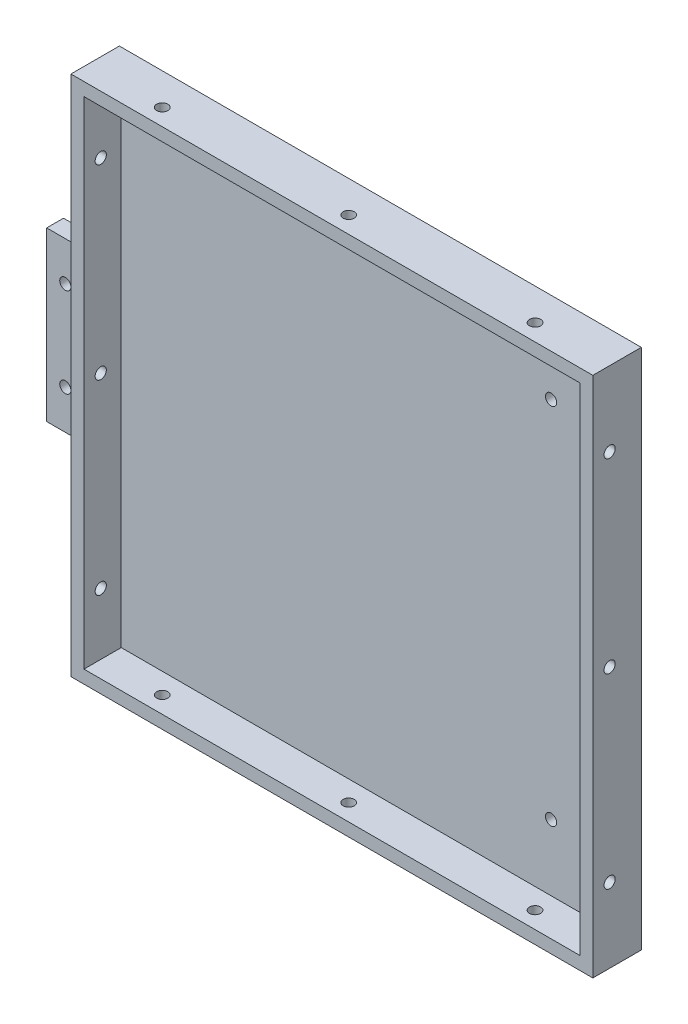
SolidWorks part; units mm, degrees
ref_plane "前视基准面" through (0, 0, 0) normal (0, 0, 1) x (1, 0, 0)
ref_plane "上视基准面" through (0, 0, 0) normal (0, 1, 0) x (1, 0, 0)
ref_plane "右视基准面" through (0, 0, 0) normal (1, 0, 0) x (0, 0, -1)
sketch "草图3" plane through (0, 0, 0) normal (0, 0, 1) x (1, 0, 0)
  line L1 (70, -70) -> (-70, -70)
  line L2 (70, -70) -> (70, 70)
  line L3 (70, 70) -> (-70, 70)
  line L4 (-70, -70) -> (-70, 70)
  line L5 (70, -70) -> (-70, 70) construction
  line L6 (70, 70) -> (-70, -70) construction
  point P0 (0, 0)
  dimension "D1" = 140
  dimension "D2" = 140
extrude "凸台-拉伸2" add sketch "草图3" along normal blind 3
sketch "草图4" plane through (0, 0, 3) normal (0, 0, 1) x (1, 0, 0)
  line L0 (70, -70) -> (70, 70) construction
  line L1 (66.5, -66.5) -> (-66.5, -66.5)
  line L2 (66.5, -66.5) -> (66.5, 66.5)
  line L3 (66.5, 66.5) -> (-66.5, 66.5)
  line L4 (-66.5, -66.5) -> (-66.5, 66.5)
  line L5 (66.5, -66.5) -> (-66.5, 66.5) construction
  line L6 (66.5, 66.5) -> (-66.5, -66.5) construction
  line L7 (-70, -70) -> (70, -70) construction
  line L12 (-70, 70) -> (-70, -70)
  line L13 (-70, -70) -> (70, -70)
  line L14 (70, -70) -> (70, 70)
  line L15 (70, 70) -> (-70, 70)
  line L16 (-70, 70) -> (-70, -70)
  line L17 (-70, -70) -> (70, -70)
  line L18 (70, -70) -> (70, 70)
  line L19 (70, 70) -> (-70, 70)
  point P0 (0, 0)
  point P6 (66.5, 0)
  dimension "D1" = 3.5
  dimension "D2" = 3.5
  dimension "D3" = 0
extrude "凸台-拉伸3" add sketch "草图4" along normal blind 10 contours L16 L17 L18 L19 | L2 L1 L4 L3
sketch "草图7" plane through (0, -70, 0) normal (0, -1, 0) x (1, 0, 0)
  line L0 (0, 13) -> (0, 8.5) construction
  line L1 (-70, 13) -> (70, 13) construction
  circle A0 centre (0, 8.5) radius 1.5
  circle A1 centre (50, 8.5) radius 1.5
  circle A2 centre (-50, 8.5) radius 1.5
  dimension "D2" = 3
  dimension "D1" = 4.5
  dimension "D3" = 2
  dimension "D4" = 2
extrude "切除-拉伸1" cut sketch "草图7" against normal through all
sketch "草图9" plane through (-70, 0, 0) normal (-1, 0, 0) x (0, 0, 1)
  line L0 (13, 0) -> (8.5, 0) construction
  line L1 (13, 70) -> (13, -70) construction
  circle A0 centre (8.5, 0) radius 1.5
  circle A1 centre (8.5, -50) radius 1.5
  circle A2 centre (8.5, 50) radius 1.5
  dimension "D2" = 3
  dimension "D1" = 4.5
  dimension "D3" = 2
  dimension "D4" = 2
extrude "切除-拉伸2" cut sketch "草图9" against normal through all
sketch "草图10" plane through (0, 0, 0) normal (0, 0, -1) x (-1, 0, 0)
  line L0 (70, -70) -> (-70, -70) construction
  line L1 (22.5, -85) -> (-22.5, -85)
  line L2 (22.5, -85) -> (22.5, -70)
  line L4 (-22.5, -85) -> (-22.5, -70)
  line L5 (22.5, -85) -> (-23.9974, -54.0017) construction
  line L6 (23.9974, -54.0017) -> (-22.5, -85) construction
  line L7 (-22.5, -70) -> (22.5, -70)
  point P0 (0, -70)
  dimension "D1" = 45
  dimension "D2" = 15
extrude "凸台-拉伸4" add sketch "草图10" against normal blind 4.5
sketch "草图11" plane through (0, 0, 4.5) normal (0, 0, 1) x (1, 0, 0)
  line L0 (0, -85) -> (0, -80)
  line L1 (22.5, -85) -> (-22.5, -85) construction
  line L2 (0, -80) -> (-12, -80) construction
  circle A0 centre (-12, -80) radius 1.5
  circle A1 centre (12, -80) radius 1.5
  dimension "D3" = 3
  dimension "D1" = 5
  dimension "D2" = 12
extrude "切除-拉伸3" cut sketch "草图11" against normal through all contours A0 | A1 region at (-12, -80, 4.5) region at (12, -80, 4.5)
sketch "草图12" plane through (0, 0, 13) normal (0, 0, 1) x (1, 0, 0)
  line L0 (-70, -70) -> (-66.5, -66.5) construction
ref_axis "基准轴1" through (0, 0, 13.65) along (0, 0, -1)
pattern_circular "阵列(圆周)1" count 2 every 90 about axis through (0, 0, 13.65) along (0, 0, -1) of "凸台-拉伸4", "切除-拉伸3"
fillet "圆角1" radius 8 6 edges at (22.5, -70, 2.25) (-22.5, -70, 2.25) (0, -70, 4.5) (-70, -22.5, 2.25) (-70, 22.5, 2.25) (-70, 0, 4.5)
sketch "草图13" plane through (-70, 0, 0) normal (-1, 0, 0) x (0, 0, 1)
  circle A0 centre (8.5, 0) radius 3
  dimension "D1" = 6
extrude "切除-拉伸4" cut sketch "草图13" along normal through all
sketch "草图14" plane through (0, -70, 0) normal (0, -1, 0) x (1, 0, 0)
  circle A0 centre (0, 8.5) radius 2.0492
extrude "切除-拉伸6" cut sketch "草图14" along normal through all contours A0
sketch "草图15" plane through (0, 0, 0) normal (0, 0, -1) x (-1, 0, 0)
  line L0 (-30.5, -70) -> (-70, -70) construction
  line L1 (-30.5, -70) -> (29.6234, -70)
  line L2 (-30.5, -70) -> (-30.5, -85.1765)
  line L3 (-30.5, -85.1765) -> (29.6234, -85.1765)
  line L4 (29.6234, -70) -> (29.6234, -85.1765)
extrude "切除-拉伸7" cut sketch "草图15" against normal blind 10
sketch "草图17" plane through (0, 0, 0) normal (0, 0, -1) x (-1, 0, 0)
  line L0 (-70, 70) -> (70, -70) construction
  line L1 (70, 70) -> (-70, -70) construction
  circle A0 centre (-48.7868, 48.7868) radius 1.505
  circle A1 centre (-48.7868, -48.7868) radius 1.505
  dimension "D1" = 3.01
  dimension "D3" = 3.01
  dimension "D2" = 30
  dimension "D4" = 30
extrude "切除-拉伸8" cut sketch "草图17" against normal blind 10
